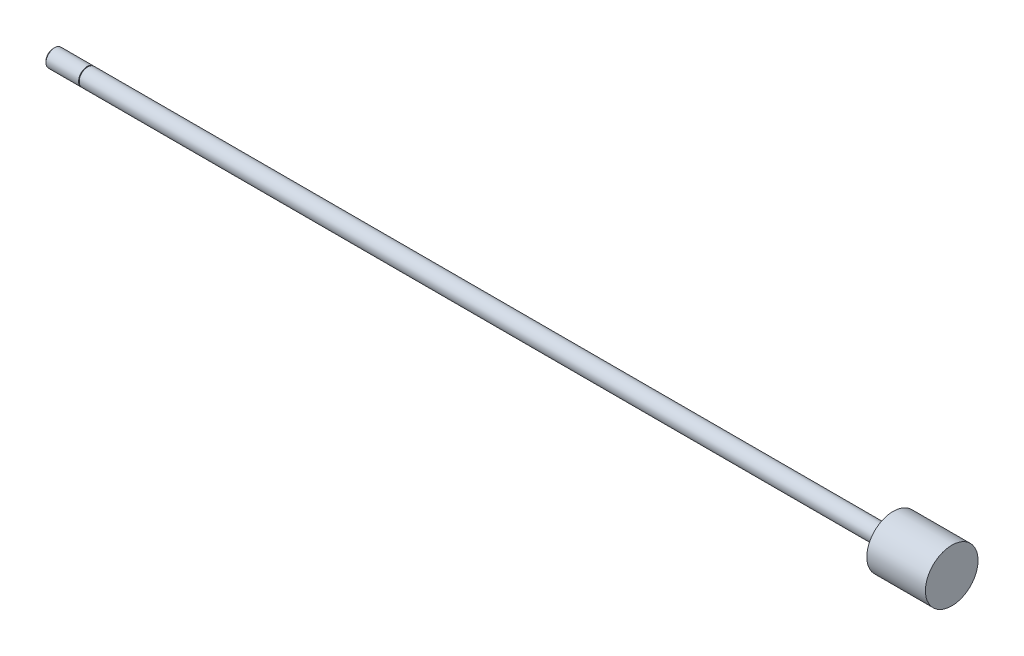
SolidWorks part; units mm, degrees
material "Plain Carbon Steel"
ref_plane "Front Plane" through (0, 0, 0) normal (0, 0, 1) x (1, 0, 0)
ref_plane "Top Plane" through (0, 0, 0) normal (0, 1, 0) x (1, 0, 0)
ref_plane "Right Plane" through (0, 0, 0) normal (1, 0, 0) x (0, 0, -1)
sketch "Sketch1" plane through (0, 0, 0) normal (0, 0, 1) x (1, 0, 0)
  line L0 (0, 0) -> (0, 3.175)
  line L1 (0, 3.175) -> (294.4876, 3.175)
  line L2 (294.4876, 3.175) -> (294.4876, 9.6203)
  line L3 (294.4876, 9.6203) -> (315.9252, 9.6203)
  line L4 (315.9252, 9.6203) -> (315.9252, 0)
  line L5 (315.9252, 0) -> (0, 0)
  line L6 (315.9252, 0) -> (0, 0) construction
revolve "Revolve1" add sketch "Sketch1" angle 360 about L6 reverse direction yes
cosmetic thread "Cosmetic Thread1" parameters "D1"=12.7, "D2"=5.268
sketch "Sketch2" plane through (0, 0, 0) normal (0, 0, 1) x (1, 0, 0)
  line L0 (-12.7, 0) -> (-12.7, 2.634)
  line L1 (-12.7, 2.634) -> (-12.159, 3.175)
  line L2 (-12.159, 3.175) -> (0, 3.175)
  line L3 (0, 3.175) -> (0, 0)
  line L4 (0, 0) -> (-12.7, 0)
  line L5 (0, 0) -> (-12.7, 0) construction
revolve "Revolve2" add sketch "Sketch2" angle 360 about L5 reverse direction yes
ref_plane "Plane1" through (0, 0, 0) normal (1, 0, 0) x (0, 0, -1)
ref_plane "Plane2" through (0, 0, 0) normal (1, 0, 0) x (0, 0, -1)
ref_plane "Plane3" through (610.4128, 0, 0) normal (1, 0, 0) x (0, 0, -1)
ref_plane "Plane4" through (-12.7, 0, 0) normal (1, 0, 0) x (0, 0, -1)
sketch "Sketch3" plane through (0, 0, 0) normal (0, 0, 1) x (1, 0, 0)
  line L0 (-0.254, 2.921) -> (0, 2.921)
  line L1 (0, 2.921) -> (0, 3.429)
  line L2 (0, 3.429) -> (-0.254, 3.429)
  line L3 (-0.254, 3.429) -> (-0.254, 2.921)
  line L4 (0, 0) -> (-0.254, 0) construction
revolve "Cut-Revolve1" cut sketch "Sketch3" angle 360 about L4 reverse direction yes
ref_plane "Plane5" through (0, 0, 0) normal (1, 0, 0) x (0, 0, -1)
ref_plane "Plane6" through (-16.764, 0, 0) normal (1, 0, 0) x (0, 0, -1)
ref_plane "dia1 XY" through (0, 0, 0) normal (1, 0, 0) x (0, 0, -1)
ref_plane "dia1 XZ" through (0, 3.175, 0) normal (0, -1, 0) x (-1, 0, 0)
ref_plane "dia1 YZ" through (0, 0, 0) normal (0, 0, -1) x (-1, 0, 0)
ref_axis "dia1 X" through (0, 3.175, 80.9) along (0, 0, -1)
ref_axis "dia1 Y" through (0, -50, 0) along (0, 1, 0)
ref_axis "dia1 Z" through (80.9, 3.175, 0) along (-1, 0, 0)
sketch3d "dia1"
  point P0 (0, 3.175, 0)
ref_plane "dia12 XY" through (0, 0, 0) normal (1, 0, 0) x (0, 0, -1)
ref_plane "dia12 XZ" through (0, 0, 0) normal (0, -1, 0) x (-1, 0, 0)
ref_plane "dia12 YZ" through (0, 0, 10.9537) normal (0, 0, -1) x (-1, 0, 0)
ref_axis "dia12 X" through (0, 0, 80.9) along (0, 0, -1)
ref_axis "dia12 Y" through (0, -50, 10.9537) along (0, 1, 0)
ref_axis "dia12 Z" through (80.9, 0, 10.9537) along (-1, 0, 0)
sketch3d "dia12"
  point P0 (0, 0, 10.9537)
ref_plane "dia2 XY" through (0, 0, 0) normal (1, 0, 0) x (0, 0, -1)
ref_plane "dia2 XZ" through (0, -3.175, 0) normal (0, -1, 0) x (-1, 0, 0)
ref_plane "dia2 YZ" through (0, 0, 0) normal (0, 0, -1) x (-1, 0, 0)
ref_axis "dia2 X" through (0, -3.175, 80.9) along (0, 0, -1)
ref_axis "dia2 Y" through (0, -50, 0) along (0, 1, 0)
ref_axis "dia2 Z" through (80.9, -3.175, 0) along (-1, 0, 0)
sketch3d "dia2"
  point P0 (0, -3.175, 0)
ref_plane "dia22 XY" through (0, 0, 0) normal (1, 0, 0) x (0, 0, -1)
ref_plane "dia22 XZ" through (0, 0, 0) normal (0, -1, 0) x (-1, 0, 0)
ref_plane "dia22 YZ" through (0, 0, -10.9537) normal (0, 0, -1) x (-1, 0, 0)
ref_axis "dia22 X" through (0, 0, 80.9) along (0, 0, -1)
ref_axis "dia22 Y" through (0, -50, -10.9537) along (0, 1, 0)
ref_axis "dia22 Z" through (80.9, 0, -10.9537) along (-1, 0, 0)
sketch3d "dia22"
  point P0 (0, 0, -10.9537)
ref_plane "rl1 XY" through (-12.7, 0, 0) normal (1, 0, 0) x (0, 0, -1)
ref_plane "rl1 XZ" through (0, 0, 0) normal (0, -1, 0) x (-1, 0, 0)
ref_plane "rl1 YZ" through (0, 0, 0) normal (0, 0, -1) x (-1, 0, 0)
ref_axis "rl1 X" through (-12.7, 0, 80.9) along (0, 0, -1)
ref_axis "rl1 Y" through (-12.7, -50, 0) along (0, 1, 0)
ref_axis "rl1 Z" through (80.9, 0, 0) along (-1, 0, 0)
sketch3d "rl1"
  point P0 (-12.7, 0, 0)
ref_plane "rl2 XY" through (0, 0, 0) normal (1, 0, 0) x (0, 0, -1)
ref_plane "rl2 XZ" through (0, 0, 0) normal (0, -1, 0) x (-1, 0, 0)
ref_plane "rl2 YZ" through (0, 0, 0) normal (0, 0, -1) x (-1, 0, 0)
ref_axis "rl2 X" through (0, 0, 80.9) along (0, 0, -1)
ref_axis "rl2 Y" through (0, -50, 0) along (0, 1, 0)
ref_axis "rl2 Z" through (80.9, 0, 0) along (-1, 0, 0)
sketch3d "rl2"
  point P0 (0, 0, 0)
ref_plane "rod_cp XY" through (0, 0, 0) normal (1, 0, 0) x (0, 0, -1)
ref_plane "rod_cp XZ" through (0, 0, 0) normal (0, -1, 0) x (-1, 0, 0)
ref_plane "rod_cp YZ" through (0, 0, 0) normal (0, 0, -1) x (-1, 0, 0)
ref_axis "rod_cp X" through (0, 0, 80.9) along (0, 0, -1)
ref_axis "rod_cp Y" through (0, -50, 0) along (0, 1, 0)
ref_axis "rod_cp Z" through (80.9, 0, 0) along (-1, 0, 0)
sketch3d "rod_cp"
  point P0 (0, 0, 0)
ref_plane "thd1 XY" through (-12.7, 0, 0) normal (1, 0, 0) x (0, 0, -1)
ref_plane "thd1 XZ" through (0, 3.175, 0) normal (0, -1, 0) x (-1, 0, 0)
ref_plane "thd1 YZ" through (0, 0, 0) normal (0, 0, -1) x (-1, 0, 0)
ref_axis "thd1 X" through (-12.7, 3.175, 80.9) along (0, 0, -1)
ref_axis "thd1 Y" through (-12.7, -50, 0) along (0, 1, 0)
ref_axis "thd1 Z" through (80.9, 3.175, 0) along (-1, 0, 0)
sketch3d "thd1"
  point P0 (-12.7, 3.175, 0)
ref_plane "thd2 XY" through (-12.7, 0, 0) normal (1, 0, 0) x (0, 0, -1)
ref_plane "thd2 XZ" through (0, -3.175, 0) normal (0, -1, 0) x (-1, 0, 0)
ref_plane "thd2 YZ" through (0, 0, 0) normal (0, 0, -1) x (-1, 0, 0)
ref_axis "thd2 X" through (-12.7, -3.175, 80.9) along (0, 0, -1)
ref_axis "thd2 Y" through (-12.7, -50, 0) along (0, 1, 0)
ref_axis "thd2 Z" through (80.9, -3.175, 0) along (-1, 0, 0)
sketch3d "thd2"
  point P0 (-12.7, -3.175, 0)
ref_plane "to_rod_clevis XY" through (-16.764, 0, 0) normal (1, 0, 0) x (0, 0, -1)
ref_plane "to_rod_clevis XZ" through (0, 0, 0) normal (0, -1, 0) x (-1, 0, 0)
ref_plane "to_rod_clevis YZ" through (0, 0, 0) normal (0, 0, -1) x (-1, 0, 0)
ref_axis "to_rod_clevis X" through (-16.764, 0, 80.9) along (0, 0, -1)
ref_axis "to_rod_clevis Y" through (-16.764, -50, 0) along (0, 1, 0)
ref_axis "to_rod_clevis Z" through (80.9, 0, 0) along (-1, 0, 0)
sketch3d "to_rod_clevis"
  point P0 (-16.764, 0, 0)
